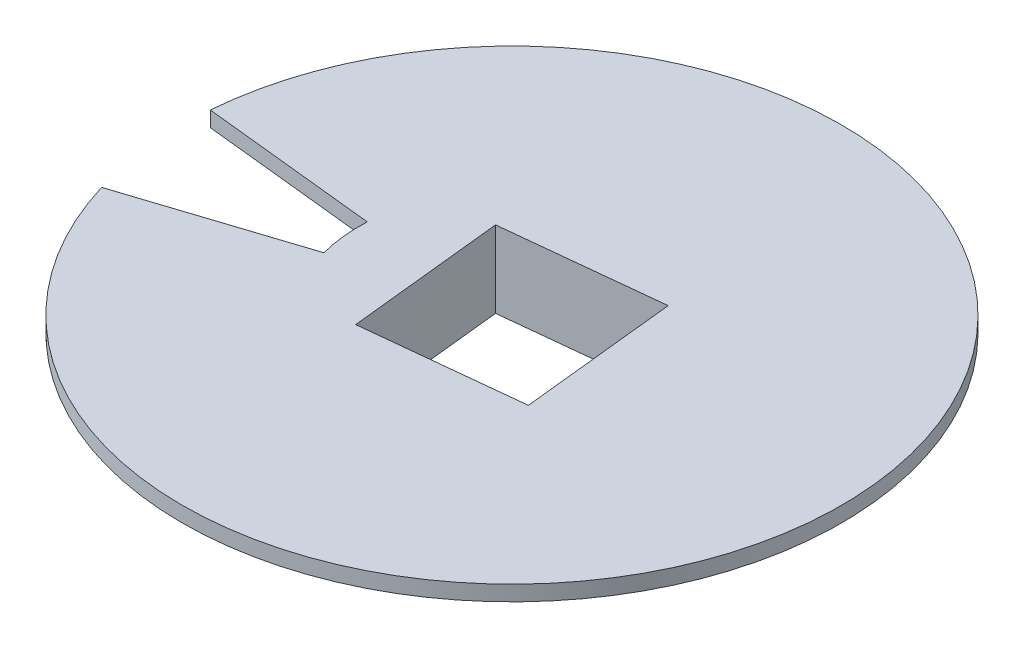
SolidWorks part; units mm, degrees
ref_plane "Front Plane" through (0, 0, 0) normal (0, 0, 1) x (1, 0, 0)
ref_plane "Top Plane" through (0, 0, 0) normal (0, 1, 0) x (1, 0, 0)
ref_plane "Right Plane" through (0, 0, 0) normal (1, 0, 0) x (0, 0, -1)
sketch "Sketch1" plane through (0, 0, 0) normal (0, 1, 0) x (1, 0, 0)
  line L0 (-1.8271, 0.8135) -> (1.8271, -0.8135)
  line L1 (-2, 0) -> (2, 0)
  line L2 (-2, 0) -> (-2, -89.9778)
  line L3 (-2, -89.9778) -> (2, -89.9778)
  line L4 (2, 0) -> (2, -89.9778)
  line L5 (-1.8271, 0.8135) -> (-38.4243, -81.3853)
  line L6 (-38.4243, -81.3853) -> (-34.7702, -83.0123)
  line L7 (1.8271, -0.8135) -> (-34.7702, -83.0123)
  line L8 (-1.3383, 1.4863) -> (1.3383, -1.4863)
  line L9 (-1.3383, 1.4863) -> (-68.2048, -58.7206)
  line L10 (-68.2048, -58.7206) -> (-65.5283, -61.6932)
  line L11 (1.3383, -1.4863) -> (-65.5283, -61.6932)
  line L12 (-0.618, 1.9021) -> (0.618, -1.9021)
  line L13 (-0.618, 1.9021) -> (-86.192, -25.9025)
  line L14 (-86.192, -25.9025) -> (-84.9559, -29.7068)
  line L15 (0.618, -1.9021) -> (-84.9559, -29.7068)
  line L16 (0.2091, 1.989) -> (-0.2091, -1.989)
  line L17 (0.2091, 1.989) -> (-89.2758, 11.3943)
  line L18 (-89.2758, 11.3943) -> (-89.6939, 7.4162)
  line L19 (-0.2091, -1.989) -> (-89.6939, 7.4162)
  line L20 (1, 1.7321) -> (-1, -1.7321)
  line L21 (1, 1.7321) -> (-76.923, 46.7209)
  line L22 (-76.923, 46.7209) -> (-78.923, 43.2568)
  line L23 (-1, -1.7321) -> (-78.923, 43.2568)
  line L24 (1.618, 1.1756) -> (-1.618, -1.1756)
  line L25 (1.618, 1.1756) -> (-51.2696, 73.9691)
  line L26 (-51.2696, 73.9691) -> (-54.5056, 71.618)
  line L27 (-1.618, -1.1756) -> (-54.5056, 71.618)
  line L28 (1.9563, 0.4158) -> (-1.9563, -0.4158)
  line L29 (1.9563, 0.4158) -> (-16.7511, 88.4274)
  line L30 (-16.7511, 88.4274) -> (-20.6637, 87.5957)
  line L31 (-1.9563, -0.4158) -> (-20.6637, 87.5957)
  line L32 (1.9563, -0.4158) -> (-1.9563, 0.4158)
  line L33 (1.9563, -0.4158) -> (20.6637, 87.5957)
  line L34 (20.6637, 87.5957) -> (16.7511, 88.4274)
  line L35 (-1.9563, 0.4158) -> (16.7511, 88.4274)
  line L36 (1.618, -1.1756) -> (-1.618, 1.1756)
  line L37 (1.618, -1.1756) -> (54.5056, 71.618)
  line L38 (54.5056, 71.618) -> (51.2696, 73.9691)
  line L39 (-1.618, 1.1756) -> (51.2696, 73.9691)
  line L40 (1, -1.7321) -> (-1, 1.7321)
  line L41 (1, -1.7321) -> (78.923, 43.2568)
  line L42 (78.923, 43.2568) -> (76.923, 46.7209)
  line L43 (-1, 1.7321) -> (76.923, 46.7209)
  line L44 (0.2091, -1.989) -> (-0.2091, 1.989)
  line L45 (0.2091, -1.989) -> (89.6939, 7.4162)
  line L46 (89.6939, 7.4162) -> (89.2758, 11.3943)
  line L47 (-0.2091, 1.989) -> (89.2758, 11.3943)
  line L48 (-0.618, -1.9021) -> (0.618, 1.9021)
  line L49 (-0.618, -1.9021) -> (84.9559, -29.7068)
  line L50 (84.9559, -29.7068) -> (86.192, -25.9025)
  line L51 (0.618, 1.9021) -> (86.192, -25.9025)
  line L52 (-1.3383, -1.4863) -> (1.3383, 1.4863)
  line L53 (-1.3383, -1.4863) -> (65.5283, -61.6932)
  line L54 (65.5283, -61.6932) -> (68.2048, -58.7206)
  line L55 (1.3383, 1.4863) -> (68.2048, -58.7206)
  line L56 (-1.8271, -0.8135) -> (1.8271, 0.8135)
  line L57 (-1.8271, -0.8135) -> (34.7702, -83.0123)
  line L58 (34.7702, -83.0123) -> (38.4243, -81.3853)
  line L59 (1.8271, 0.8135) -> (38.4243, -81.3853)
  circle A1 centre (0, 0) radius 90
  point P7 (0, 0)
  point P126 (0, 0)
  dimension "D1" = 180
  dimension "D2" = 4
  dimension "D3" = 15
sketch "Sketch7" plane through (0, 0, 0) normal (0, 0, 1) x (1, 0, 0)
  line L6 (0, 0) -> (-86, 0)
  line L7 (0, 0) -> (0, -4)
  line L8 (0, -4) -> (-86, -4)
  line L9 (-86, 0) -> (-86, -4)
  dimension "D1" = 4
  dimension "D2" = 86
revolve "Revolve4" add sketch "Sketch7" angle 360 about L7
sketch "Sketch9" plane through (0, 0, 0) normal (0, 1, 0) x (1, 0, 0)
  circle A0 centre (0, 0) radius 40
  dimension "D1" = 80
extrude "Cut-Extrude3" cut sketch "Sketch9" against normal through all and the other way through all
extrude "Cut-Extrude4" cut sketch "Sketch1" against normal through all contours L19 A1 L13 region at (-62.5121, 0, 6.5703)
ref_plane "Plane1" through (0, 0, 0) normal (0, -1, 0) x (-1, 0, 0)
sketch "Sketch10" plane through (0, 0, 0) normal (0, -1, 0) x (-1, 0, 0)
  circle A0 centre (0, 0) radius 40
extrude "Boss-Extrude1" add sketch "Sketch10" along normal blind 20
sketch "Sketch14" plane through (0, 0, 0) normal (0, 1, 0) x (1, 0, 0)
  line L0 (-39.7809, -4.1811) -> (0, 0) construction
  line L1 (18.2449, 22.5305) -> (-22.5305, 18.2449)
  line L2 (-22.5305, 18.2449) -> (-18.2449, -22.5305)
  line L3 (-18.2449, -22.5305) -> (22.5305, -18.2449)
  line L4 (22.5305, -18.2449) -> (18.2449, 22.5305)
  arc A1 (-39.9402, 2.1869) -> (-38.6127, -10.4431) centre (0, 0) ccw construction
  arc A10 (-39.9402, 2.1869) -> (-38.6127, -10.4431) centre (0, 0) ccw construction
  dimension "D3" = 20.5
  dimension "D1" = 41
  dimension "D2" = 20.5
extrude "Cut-Extrude7" cut sketch "Sketch14" against normal through all contours L3 L4 L1 L2 region at (0, 0, 0)
